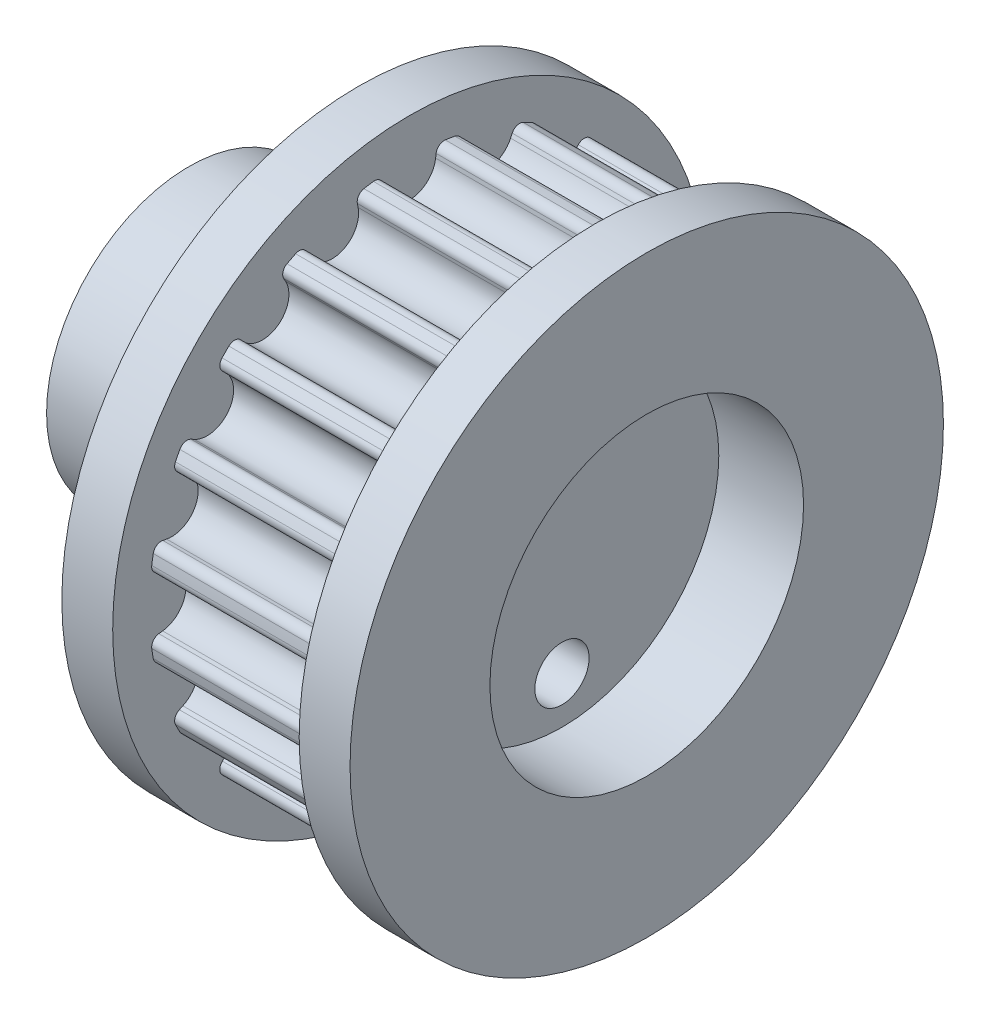
SolidWorks part; units mm, degrees
ref_plane "前视基准面" through (0, 0, 0) normal (0, 0, 1) x (1, 0, 0)
ref_plane "上视基准面" through (0, 0, 0) normal (0, 1, 0) x (1, 0, 0)
ref_plane "右视基准面" through (0, 0, 0) normal (1, 0, 0) x (0, 0, -1)
sketch "草图1" plane through (0, 0, 0) normal (0, 0, 1) x (1, 0, 0)
  line L0 (0, 0) -> (64.8368, 0) construction
  line L1 (0, 3.0686) -> (0, 15.343)
  line L2 (0, 15.343) -> (28, 15.343)
  line L3 (28, 15.343) -> (28, 6.1372)
  line L4 (28, 6.1372) -> (20, 6.1372)
  line L5 (20, 6.1372) -> (20, 3.0686)
  line L6 (20, 3.0686) -> (0, 3.0686)
  dimension "L" = 20
  dimension "B" = 28
  dimension "d" = 6.1372
  dimension "d1" = 12.2744
  dimension "da" = 30.686
revolve "旋转1" add sketch "草图1" angle 360 about L0
chamfer "倒角1" distance 1 angle 45 2 edges at (20, 0, 3.0686) (0, 0, 3.0686)
sketch "草图4" plane through (0, 0, 0) normal (-1, 0, 0) x (0, 0, 1)
  line L1 (-1, 2.9011) -> (1, 2.9011)
  line L2 (-1, 2.9011) -> (-1, 3.9011)
  line L3 (-1, 3.9011) -> (1, 3.9011)
  line L4 (1, 2.9011) -> (1, 3.9011)
  circle A0 centre (0, 0) radius 3.0686 construction
  dimension "键槽宽度" = 2
  dimension "t1" = 1
extrude "切除-拉伸1" cut sketch "草图4" against normal through all
ref_axis "基准轴1" through (-1.4, 0, 0) along (1, 0, 0)
sketch "草图6" plane through (0, 0, 0) normal (1, 0, 0) x (0, 0, -1)
  line L0 (0, 0) -> (0, 30.6512) construction
  line L1 (1.5761, 14.7791) -> (1.5484, 14.5529)
  line L2 (2.5932, 15.1223) -> (6.4026, 46.1473)
  line L3 (-2.5932, 15.1223) -> (-6.4026, 46.1473)
  line L4 (-1.5761, 14.7791) -> (-1.5484, 14.5529)
  circle A0 centre (0, 0) radius 15.343 construction
  circle A1 centre (0, 0) radius 13.183 construction
  arc A2 (-1.5484, 14.5529) -> (1.5484, 14.5529) centre (0, 14.743) ccw
  arc A3 (6.4026, 46.1473) -> (-6.4026, 46.1473) centre (0, 0) ccw
  arc A4 (1.5761, 14.7791) -> (2.1189, 15.196) centre (2.0526, 14.7206) cw
  arc A5 (2.1189, 15.196) -> (2.5932, 15.1223) centre (0, 0) cw
  arc A6 (-2.1189, 15.196) -> (-2.5932, 15.1223) centre (0, 0) ccw
  arc A7 (-1.5761, 14.7791) -> (-2.1189, 15.196) centre (-2.0526, 14.7206) ccw
  point P7 (0, 3.25)
  point P8 (0, 28.4912)
  point P15 (1.6347, 15.2557)
  dimension "D1" = 26.366
  dimension "ra" = 0.48
  dimension "rf" = 1.56
  dimension "hg" = 2.16
  dimension "D3" = 0.48
  dimension "D4" = 31.258
  dimension "angle" = 14
  dimension "bw" = 3.25
extrude "切除-拉伸2" cut sketch "草图6" along normal up to next
pattern_circular "阵列(圆周)3" count 20 over 360 about axis through (-1.4, 0, 0) along (1, 0, 0) of "切除-拉伸2"
sketch "草图7" plane through (28, 0, 0) normal (1, 0, 0) x (0, 0, -1)
  circle A0 centre (0, 0) radius 6.1372
sketch "草图8" plane through (28, 0, 0) normal (1, 0, 0) x (0, 0, -1)
  circle A0 centre (0, 0) radius 17.5309
extrude "切除-拉伸3" cut sketch "草图8" against normal offset from surface (17 mm away) 11 up to face at (0, 0, -4.0686)
sketch "草图9" plane through (11, 0, 0) normal (1, 0, 0) x (0, 0, -1)
  circle A0 centre (0, 0) radius 7.0115
extrude "凸台-拉伸1" add sketch "草图9" against normal up to surface (11 mm away) up to face at (0, 0, -4.0686)
sketch "草图10" plane through (11, 0, 0) normal (1, 0, 0) x (0, 0, -1)
  circle A0 centre (0, 0) radius 17.5
  dimension "D1" = 35
extrude "凸台-拉伸2" add sketch "草图10" along normal blind 3
sketch "草图11" plane through (0, 0, 0) normal (-1, 0, 0) x (0, 0, 1)
  circle A0 centre (0, 0) radius 17.5
  dimension "D1" = 35
extrude "凸台-拉伸3" add sketch "草图11" along normal blind 3
sketch "草图12" plane through (14, 0, 0) normal (1, 0, 0) x (0, 0, -1)
  circle A0 centre (0, 0) radius 9.25
  dimension "D1" = 18.5
extrude "切除-拉伸4" cut sketch "草图12" against normal blind 5
sketch "草图13" plane through (9, 0, 0) normal (1, 0, 0) x (0, 0, -1)
  circle A0 centre (0, 0) radius 6.5 construction
  circle A1 centre (0, 6.5) radius 1.6
  circle A2 centre (0, -6.5) radius 1.6
  dimension "D1" = 13
  dimension "D2" = 3.2
  dimension "D3" = 3.2
extrude "切除-拉伸5" cut sketch "草图13" against normal through all
sketch "草图14" plane through (-3, 0, 0) normal (-1, 0, 0) x (0, 0, 1)
  circle A0 centre (0, 0) radius 12
  circle A1 centre (0, 6.5) radius 3.5
  circle A2 centre (0, -6.5) radius 3.5
  circle M1 centre (0, 6.5) radius 1.6
  circle M2 centre (0, -6.5) radius 1.6
  dimension "D1" = 24
  dimension "D2" = 7
  dimension "D3" = 7
extrude "凸台-拉伸4" add sketch "草图14" along normal blind 3 contours A2 M2 | A1 M1 | A0 A2 A1 region at (-3, 0, 0) region at (-3, 6.5, -3.401) region at (-3, -6.5, -3.401)
sketch "草图17" plane through (-6, 0, 0) normal (-1, 0, 0) x (0, 0, 1)
  circle A0 centre (0, 0) radius 8.4
  dimension "D1" = 16.8
extrude "凸台-拉伸6" add sketch "草图17" along normal blind 7
sketch "草图18" plane through (9, 0, 0) normal (1, 0, 0) x (0, 0, -1)
  circle A0 centre (0, 6.5) radius 1.6 construction
  circle A1 centre (0, 6.5) radius 1.6
  circle A2 centre (0, -6.5) radius 1.6 construction
  circle A3 centre (0, -6.5) radius 1.6
extrude "切除-拉伸7" cut sketch "草图18" against normal through all
equation "\"D1@草图6\" = \"da@草图1\"  - \"hg@草图6\" - \"hg@草图6\""
equation "\"D3@草图6\" = \"ra@草图6\""
